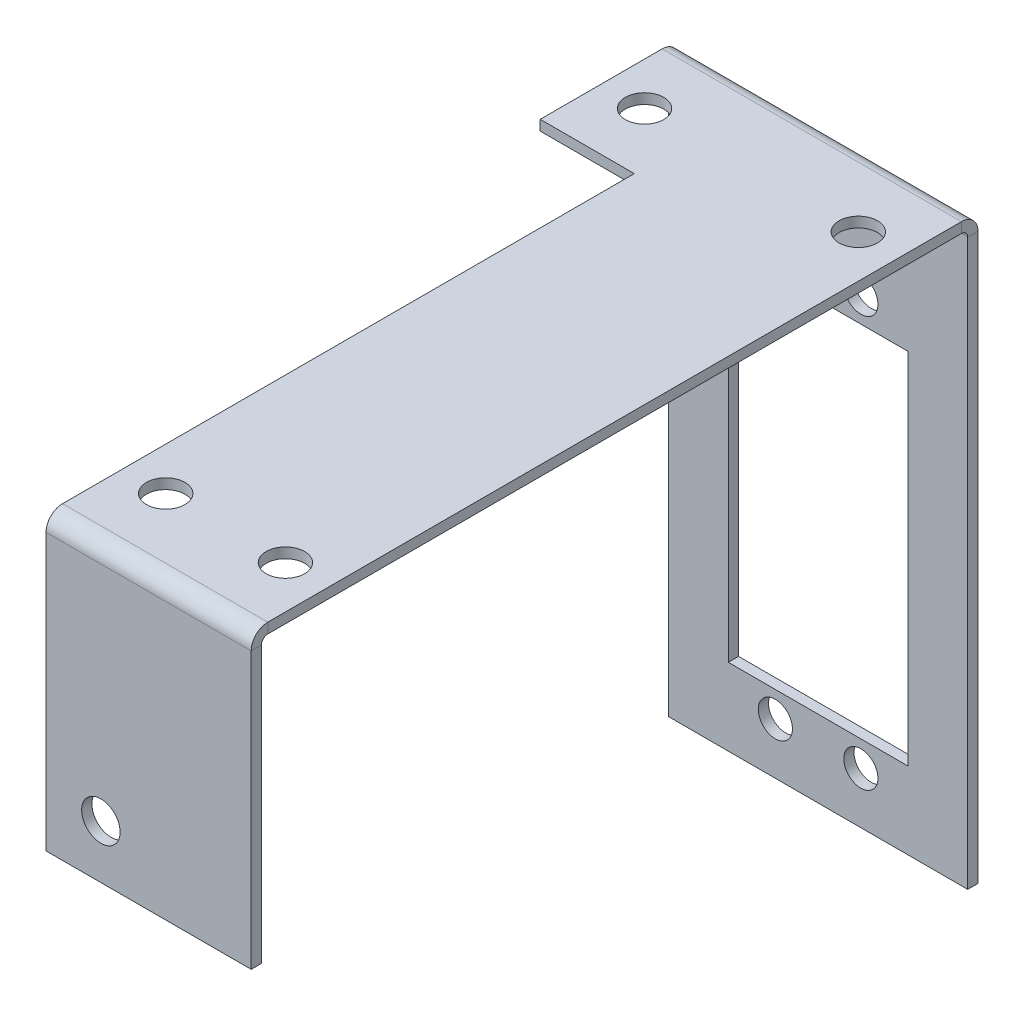
SolidWorks part; units mm, degrees
note: The reader was unsure of these and kept them because the rebuilt part matched: flange length of "Ребро-кромка1", "Ребро-кромка2".
ref_plane "Спереди" through (0, 0, 0) normal (0, 0, 1) x (1, 0, 0)
ref_plane "Сверху" through (0, 0, 0) normal (0, 1, 0) x (1, 0, 0)
ref_plane "Справа" through (0, 0, 0) normal (1, 0, 0) x (0, 0, -1)
sketch "Эскиз1" plane through (0, 0, 0) normal (0, 0, 1) x (1, 0, 0)
  line L0 (10.5, 42) -> (10.5, 45) construction
  line L1 (0, 0) -> (21, 0)
  line L2 (0, 0) -> (0, 42)
  line L3 (0, 42) -> (21, 42)
  line L4 (21, 0) -> (21, 42)
  line L5 (5.5, 45) -> (15.5, 45) construction
  line L6 (10.5, 0) -> (10.5, -3) construction
  line L7 (5.5, -3) -> (15.5, -3) construction
  line L8 (10.5, 0) -> (10.5, -9) construction
  line L9 (28, 59) -> (-7, 59)
  line L10 (28, 59) -> (28, -9)
  line L11 (28, -9) -> (-7, -9)
  line L12 (-7, 59) -> (-7, -9)
  circle A0 centre (5.5, 45) radius 2
  circle A1 centre (15.5, 45) radius 2
  circle A2 centre (5.5, -3) radius 2
  circle A3 centre (15.5, -3) radius 2
  dimension "D6" = 4
  dimension "D1" = 21
  dimension "D2" = 42
  dimension "D3" = 48
  dimension "D4" = 3
  dimension "D5" = 10
  dimension "D7" = 35
  dimension "D8" = 17
  dimension "D9" = 9
base flange "Базовая кромка1" sketch "Эскиз1" thickness 1.2 reverse thickness direction no parameters "D1"=0.7366
edge flange "Ребро-кромка1" sketch "Эскиз8" flange angle 90 flange length 85 flange position material inside bend radius 0.7366 thickness 1.2 relief rectangular parameters "D6"=10
sketch "Эскиз8" plane through (0, 59, 0) normal (0, 1, 0) x (-1, 0, 0)
  line L0 (-28, 0) -> (7, 0) construction
  line L1 (-28, 0) -> (7, 0)
  line L2 (-28, 0) -> (-28, 83.8)
  line L3 (-28, 83.8) -> (-4, 83.8)
  line L4 (7, 15) -> (7, 0)
  line L6 (7, 15) -> (-4, 15)
  line L9 (-4, 15) -> (-4, 83.8)
  dimension "D1" = 11
  dimension "D2" = 15
  dimension "D3" = 83.8
bend "EdgeBend1" bend radius 0.7366 bend angle 90 parameters "D5"=1
edge flange "Ребро-кромка2" sketch "Эскиз11" flange angle 90 flange length 34.2 flange position material inside bend radius 0.7366 thickness 1.2 relief rectangular parameters "D6"=10
sketch "Эскиз11" plane through (0, 57.8, 83.8) normal (0, 0, -1) x (1, 0, 0)
  line L1 (28, 0) -> (4, 0) construction
  line L2 (4, 0) -> (4, 33)
  line L3 (4, 33) -> (28, 33)
  line L4 (28, 33) -> (28, 0)
  line L5 (28, 0) -> (4, 0)
  dimension "D1" = 33
bend "EdgeBend2" bend radius 0.7366 bend angle 90 parameters "D5"=2
sketch "Эскиз12" plane through (0, 0, 83.8) normal (0, 0, 1) x (1, 0, 0)
  line L0 (4, 59) -> (28, 59) construction
  line L1 (4, 24.8) -> (4, 57.0634) construction
  circle A0 centre (10.42, 31.03) radius 2.25
  dimension "D3" = 4.5
  dimension "D1" = 27.97
  dimension "D2" = 6.42
extrude "Вырез-Вытянуть1" cut sketch "Эскиз12" against normal up to next normal cut yes
sketch "Эскиз13" plane through (0, 59, 0) normal (0, 1, 0) x (1, 0, 0)
  line L0 (-7, -7.8) -> (28, -7.8) construction
  line L1 (-7, -15) -> (-7, 0) construction
  line L2 (28, -81.8634) -> (28, -0.7366) construction
  line L3 (4, -74.8) -> (28, -74.8) construction
  line L4 (4, -15) -> (4, -81.8634) construction
  line L5 (-7, 1.2) -> (28, 1.2) construction
  line L6 (28, -83.8) -> (4, -83.8) construction
  line L7 (-7, -0.7366) -> (-7, -15) construction
  circle A0 centre (23, -7.8) radius 2.25
  circle A1 centre (-2, -7.8) radius 2.25
  circle A2 centre (9, -74.8) radius 2.25
  circle A3 centre (23, -74.8) radius 2.25
  dimension "D3" = 5
  dimension "D4" = 5
  dimension "D5" = 4.5
  dimension "D6" = 5
  dimension "D7" = 5
  dimension "D1" = 9
  dimension "D2" = 9
extrude "Вырез-Вытянуть2" cut sketch "Эскиз13" against normal up to next normal cut yes
sketch "Сгиб-Линии1" plane through (0, 0, 0) normal (0, 1, 0) x (1, 0, 0)
sketch "Граничная рамка1" plane through (0, 0, 0) normal (0, 1, 0) x (1, 0, 0)
sheet metal parameters "Листовой металл3" thickness 1.2 parameters "D1"=0.7366
flat pattern "Развертка3" [suppressed]
sketch "Сгиб-Линии2" plane through (0, 0, 0) normal (0, 1, 0) x (1, 0, 0)
sketch "Граничная рамка2" [suppressed] plane through (0, 0, 0) normal (0, 1, 0) x (1, 0, 0)
sheet metal parameters "Листовой металл4" thickness 1.2 parameters "D1"=0.7366
flat pattern "Развертка3" [suppressed]
sketch "Сгиб-Линии2" plane through (0, 0, 0) normal (0, 1, 0) x (1, 0, 0)
sketch "Граничная рамка2" [suppressed] plane through (0, 0, 0) normal (0, 1, 0) x (1, 0, 0)
bend of the flat pattern "Плоское состояние-<EdgeBend1>1"
sheet metal parameters "Листовой металл5" thickness 1.2 parameters "D1"=0.7366
flat pattern "Развертка3" [suppressed]
sketch "Сгиб-Линии2" plane through (0, 0, 0) normal (0, 1, 0) x (1, 0, 0)
sketch "Граничная рамка2" [suppressed] plane through (0, 0, 0) normal (0, 1, 0) x (1, 0, 0)
bend of the flat pattern "Плоское состояние-<EdgeBend1>1"
bend of the flat pattern "Плоское состояние-<EdgeBend2>1"
sheet metal parameters "Листовой металл6" thickness 1.2 parameters "D1"=0.7366
flat pattern "Развертка3" [suppressed]
sketch "Сгиб-Линии2" plane through (0, 0, 0) normal (0, 1, 0) x (1, 0, 0)
sketch "Граничная рамка2" [suppressed] plane through (0, 0, 0) normal (0, 1, 0) x (1, 0, 0)
bend of the flat pattern "Плоское состояние-<EdgeBend1>1"
bend of the flat pattern "Плоское состояние-<EdgeBend2>1"
sheet metal parameters "Листовой металл7" thickness 1.2 parameters "D1"=0.7366
flat pattern "Развертка3" [suppressed]
sketch "Сгиб-Линии2" plane through (0, 0, 0) normal (0, 1, 0) x (1, 0, 0)
sketch "Граничная рамка2" [suppressed] plane through (0, 0, 0) normal (0, 1, 0) x (1, 0, 0)
bend of the flat pattern "Плоское состояние-<EdgeBend1>1"
bend of the flat pattern "Плоское состояние-<EdgeBend2>1"
